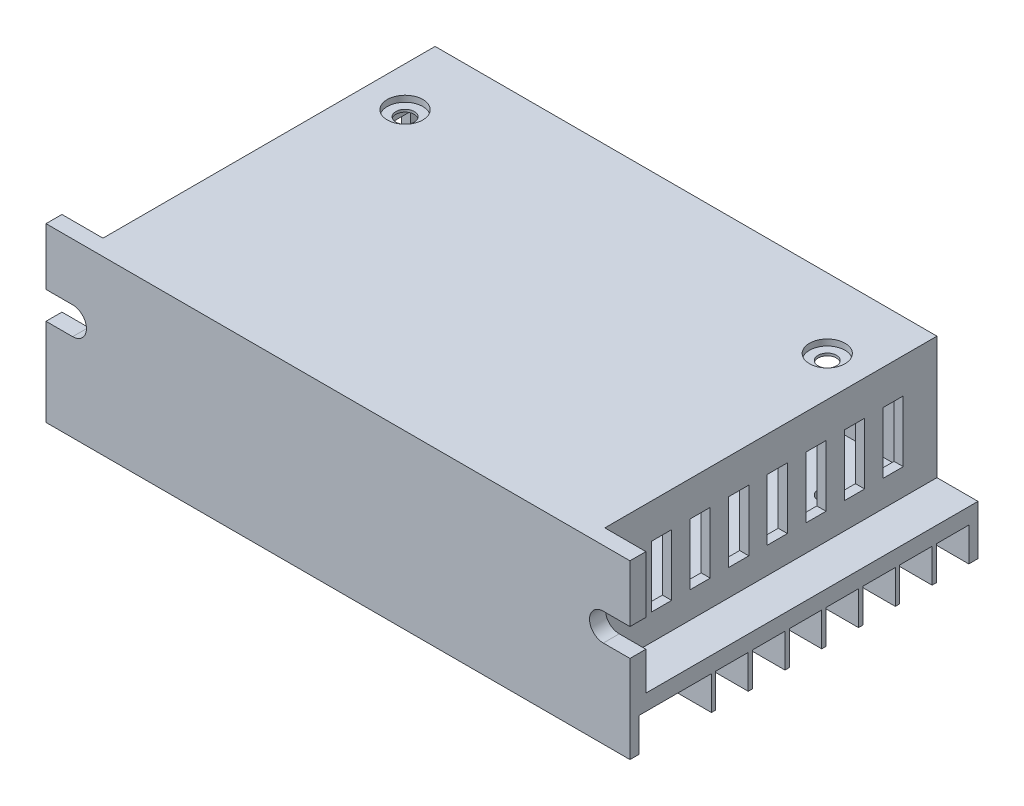
SolidWorks part; units mm, degrees
ref_plane "Front Plane" through (0, 0, 0) normal (0, 0, 1) x (1, 0, 0)
ref_plane "Top Plane" through (0, 0, 0) normal (0, 1, 0) x (1, 0, 0)
ref_plane "Right Plane" through (0, 0, 0) normal (1, 0, 0) x (0, 0, -1)
sketch "Sketch1" plane through (0, 0, 0) normal (0, 1, 0) x (1, 0, 0)
  line L1 (-47.65, 28.4) -> (47.65, 28.4)
  line L2 (-47.65, 28.4) -> (-47.65, -28.4)
  line L3 (-47.65, -28.4) -> (47.65, -28.4)
  line L4 (47.65, 28.4) -> (47.65, -28.4)
  line L5 (-47.65, 28.4) -> (47.65, -28.4) construction
  line L6 (-47.65, -28.4) -> (47.65, 28.4) construction
  point P0 (0, 0)
  dimension "D1" = 95.3
  dimension "D2" = 56.8
extrude "Boss-Extrude1" add sketch "Sketch1" along normal blind 28.1
sketch "Sketch2" plane through (-47.65, 0, 0) normal (-1, 0, 0) x (0, 0, 1)
  line L0 (-26.9, 0) -> (-26.9, 5.5)
  line L1 (-28.4, 0) -> (28.4, 0) construction
  line L2 (-26.9, 5.5) -> (-28.4, 5.5)
  line L3 (-28.4, 28.1) -> (-28.4, 0) construction
  line L4 (-28.4, 5.5) -> (-28.4, 0)
  line L5 (-28.4, 0) -> (-26.9, 0)
  line L6 (-15.6, 5.5) -> (-14.9, 5.5)
  line L7 (-21.6, 5.5) -> (-20.9, 5.5)
  line L8 (-21.6, 5.5) -> (-21.6, 0)
  line L9 (-21.6, 0) -> (-20.9, 0)
  line L10 (-20.9, 5.5) -> (-20.9, 0)
  line L11 (-15.6, 5.5) -> (-15.6, 0)
  line L12 (-14.9, 5.5) -> (-14.9, 0)
  line L13 (-15.6, 0) -> (-14.9, 0)
  line L14 (-9.6, 5.5) -> (-8.9, 5.5)
  line L15 (-9.6, 5.5) -> (-9.6, 0)
  line L16 (-8.9, 5.5) -> (-8.9, 0)
  line L17 (-9.6, 0) -> (-8.9, 0)
  line L18 (-3.6, 5.5) -> (-2.9, 5.5)
  line L19 (-3.6, 5.5) -> (-3.6, 0)
  line L20 (-2.9, 5.5) -> (-2.9, 0)
  line L21 (-3.6, 0) -> (-2.9, 0)
  line L22 (2.4, 5.5) -> (3.1, 5.5)
  line L23 (2.4, 5.5) -> (2.4, 0)
  line L24 (3.1, 5.5) -> (3.1, 0)
  line L25 (2.4, 0) -> (3.1, 0)
  line L26 (8.4, 5.5) -> (9.1, 5.5)
  line L27 (8.4, 5.5) -> (8.4, 0)
  line L28 (9.1, 5.5) -> (9.1, 0)
  line L29 (8.4, 0) -> (9.1, 0)
  line L30 (14.4, 5.5) -> (15.1, 5.5)
  line L31 (14.4, 5.5) -> (14.4, 0)
  line L32 (15.1, 5.5) -> (15.1, 0)
  line L33 (14.4, 0) -> (15.1, 0)
  line L35 (28.4, 0) -> (26.9, 0)
  line L36 (28.4, 0) -> (28.4, 5.5)
  line L37 (28.4, 5.5) -> (26.9, 5.5)
  line L38 (26.9, 0) -> (26.9, 5.5)
  line L39 (-28.4, 5.5) -> (28.4, 5.5)
  line L40 (-28.4, 5.5) -> (-28.4, 0)
  line L41 (-28.4, 0) -> (28.4, 0)
  line L42 (28.4, 5.5) -> (28.4, 0)
  line M25 (-28.4, 0) -> (28.4, 0)
  dimension "D1" = 1.5
  dimension "D2" = 5.5
  dimension "D3" = 0.7
  dimension "D4" = 5.3
  dimension "D5" = 7
extrude "Cut-Extrude2" cut sketch "Sketch2" against normal through all contours L39 L0 L8 M25 | L39 L10 L11 M25 | L39 L12 L15 M25 | L39 L16 L19 M25 | L39 L20 L23 M25 | L39 L24 L27 M25 | L39 L28 L31 M25 | L39 L32 L38 M25 region at (-47.65, 2.75, -24.25) region at (-47.65, 2.75, -18.25) region at (-47.65, 2.75, -12.25) region at (-47.65, 2.75, -6.25) region at (-47.65, 2.75, -0.25) region at (-47.65, 2.75, 5.75) region at (-47.65, 2.75, 11.75) region at (-47.65, 2.75, 21)
sketch "Sketch3" plane through (0, 0, -28.4) normal (0, 0, -1) x (-1, 0, 0)
  line L0 (-47.65, 28.1) -> (47.65, 28.1) construction
  line L1 (-40.95, 28.1) -> (40.95, 28.1)
  line L2 (-40.95, 28.1) -> (-40.95, 8.1)
  line L3 (-40.95, 8.1) -> (40.95, 8.1)
  line L4 (40.95, 28.1) -> (40.95, 8.1)
  line L5 (-47.65, 0) -> (47.65, 0) construction
  line L6 (47.65, 28.1) -> (47.65, 0) construction
  line L7 (-47.65, 28.1) -> (47.65, 28.1)
  line L8 (-47.65, 28.1) -> (-47.65, 8.1)
  line L9 (-47.65, 8.1) -> (47.65, 8.1)
  line L10 (47.65, 28.1) -> (47.65, 8.1)
  point P9 (0, 8.1)
  line M10 (47.65, 0) -> (47.65, 28.1)
  line M11 (47.65, 28.1) -> (-47.65, 28.1)
  line M12 (-47.65, 28.1) -> (-47.65, 0)
  dimension "D1" = 81.9
  dimension "D2" = 8.1
extrude "Cut-Extrude4" cut sketch "Sketch3" against normal offset from surface (54.2 mm away) 2.6 contours L9 L2 M12 M11 | L4 L9 M10 M11 region at (44.3, 18.1, -28.4) region at (-44.3, 18.1, -28.4) up to face at (0, 14.05, 28.4)
sketch "Sketch4" plane through (0, 0, 28.4) normal (0, 0, 1) x (1, 0, 0)
  line L0 (43.3, 16.55) -> (52, 16.55) construction
  line L1 (43.3, 18.8) -> (52, 18.8)
  line L2 (43.3, 14.3) -> (52, 14.3)
  line L3 (47.65, 28.1) -> (47.65, 0) construction
  line L4 (-47.65, 28.1) -> (47.65, 28.1) construction
  arc A0 (43.3, 18.8) -> (43.3, 14.3) centre (43.3, 16.55) ccw
  arc A1 (52, 14.3) -> (52, 18.8) centre (52, 16.55) ccw
  point P2 (47.65, 16.55)
  dimension "D2" = 4.35
  dimension "D1" = 4.5
  dimension "D3" = 9.3
extrude "Cut-Extrude5" cut sketch "Sketch4" against normal through all
mirror "Mirror1" about plane through (0, 0, 0) normal (1, 0, 0) of "Cut-Extrude5"
sketch "Sketch5" plane through (40.95, 0, 0) normal (1, 0, 0) x (0, 0, -1)
  line L0 (-25.8, 28.1) -> (28.4, 28.1) construction
  line L1 (-18.2, 22.4) -> (-14.9, 22.4)
  line L2 (-18.2, 22.4) -> (-18.2, 12.4)
  line L3 (-18.2, 12.4) -> (-14.9, 12.4)
  line L4 (-14.9, 22.4) -> (-14.9, 12.4)
  line L5 (-28.4, 14.3) -> (-28.4, 0) construction
  line L6 (-11.9, 22.4) -> (-8.6, 22.4)
  line L7 (-11.9, 22.4) -> (-11.9, 12.4)
  line L8 (-11.9, 12.4) -> (-8.6, 12.4)
  line L9 (-8.6, 22.4) -> (-8.6, 12.4)
  line L10 (-5.6, 22.4) -> (-2.3, 22.4)
  line L11 (-5.6, 22.4) -> (-5.6, 12.4)
  line L12 (-5.6, 12.4) -> (-2.3, 12.4)
  line L13 (-2.3, 22.4) -> (-2.3, 12.4)
  line L14 (0.7, 22.4) -> (4, 22.4)
  line L15 (0.7, 22.4) -> (0.7, 12.4)
  line L16 (0.7, 12.4) -> (4, 12.4)
  line L17 (4, 22.4) -> (4, 12.4)
  line L18 (7, 22.4) -> (10.3, 22.4)
  line L19 (7, 22.4) -> (7, 12.4)
  line L20 (7, 12.4) -> (10.3, 12.4)
  line L21 (10.3, 22.4) -> (10.3, 12.4)
  line L22 (13.3, 22.4) -> (16.6, 22.4)
  line L23 (13.3, 22.4) -> (13.3, 12.4)
  line L24 (13.3, 12.4) -> (16.6, 12.4)
  line L25 (16.6, 22.4) -> (16.6, 12.4)
  line L26 (19.6, 22.4) -> (22.9, 22.4)
  line L27 (19.6, 22.4) -> (19.6, 12.4)
  line L28 (19.6, 12.4) -> (22.9, 12.4)
  line L29 (22.9, 22.4) -> (22.9, 12.4)
  dimension "D1" = 10
  dimension "D2" = 5.7
  dimension "D3" = 3.3
  dimension "D4" = 10.2
  dimension "D5" = 7
extrude "Cut-Extrude6" cut sketch "Sketch5" against normal through all
sketch "Sketch6" plane through (0, 28.1, 0) normal (0, 1, 0) x (1, 0, 0)
  line L8 (-39.45, -25.8) -> (39.45, -25.8)
  line L9 (-40.95, -25.8) -> (-47.65, -25.8) construction
  line L16 (39.45, -26.9) -> (39.45, 26.9)
  line L17 (39.45, 26.9) -> (-39.45, 26.9)
  line L18 (-39.45, 26.9) -> (-39.45, -26.9)
  line L19 (-39.45, -26.9) -> (39.45, -26.9)
  line L20 (39.45, -25.8) -> (39.45, 26.9)
  line L21 (39.45, 26.9) -> (-39.45, 26.9)
  line L22 (-39.45, 26.9) -> (-39.45, -25.8)
  dimension "D1" = 1.5
extrude "Cut-Extrude8" cut sketch "Sketch6" against normal up to surface (20 mm away) from offset 1.4 up to face at (-44.3, 8.1, -1.3) offset against normal yes
sketch "Sketch7" plane through (-40.95, 0, 0) normal (-1, 0, 0) x (0, 0, 1)
  line L0 (-28.4, 28.1) -> (-28.4, 8.1) construction
  line L1 (-12.5, 25) -> (6.5, 25)
  line L2 (-12.5, 25) -> (-12.5, 14.5)
  line L3 (-12.5, 14.5) -> (6.5, 14.5)
  line L4 (6.5, 25) -> (6.5, 14.5)
  line L5 (25.8, 28.1) -> (-28.4, 28.1) construction
  line L6 (25.8, 8.1) -> (-28.4, 8.1) construction
  line L7 (25.8, 8.1) -> (25.8, 28.1) construction
  dimension "D1" = 15.9
  dimension "D2" = 3.1
  dimension "D3" = 6.4
  dimension "D4" = 19.3
extrude "Cut-Extrude9" cut sketch "Sketch7" against normal up to next
sketch "Sketch8" plane through (0, 0, -28.4) normal (0, 0, -1) x (-1, 0, 0)
  line L0 (-40.95, 28.1) -> (40.95, 28.1) construction
  line L1 (-33.15, 24.3) -> (33.15, 24.3)
  line L2 (-33.15, 24.3) -> (-33.15, 13.5)
  line L3 (-33.15, 13.5) -> (33.15, 13.5)
  line L4 (33.15, 24.3) -> (33.15, 13.5)
  point P4 (0, 24.3)
  dimension "D1" = 66.3
  dimension "D2" = 10.8
  dimension "D3" = 3.8
extrude "Cut-Extrude10" cut sketch "Sketch8" against normal up to next
sketch "Sketch9" plane through (0, 28.1, 0) normal (0, 1, 0) x (1, 0, 0)
  line L0 (-40.95, -25.8) -> (-40.95, 28.4) construction
  line L1 (40.95, 28.4) -> (-40.95, 28.4) construction
  point P0 (-34.45, 17)
  dimension "D1" = 6.5
  dimension "D2" = 11.4
hole_wizard "CBORE for M5 Hex Head Bolt1" positions "Sketch9" profile "Sketch10" counterbore size "M5" standard "ANSI Metric" end condition through all
sketch "Sketch10" plane through (-34.45, 28.1, -17) normal (1, 0, 0) x (0, 0, 1)
  line L0 (0, 0) -> (0, 28.1)
  line L1 (0, 28.1) -> (1.5, 28.1)
  line L3 (1.5, 28.1) -> (1.5, 1)
  line L4 (1.5, 1) -> (2.9, 1)
  line L5 (2.9, 1) -> (2.9, 0)
  line L7 (2.9, 0) -> (0, 0)
  line L11 (0, -6.35) -> (0, 107.95) construction
  dimension "Thru Hole Dia." = 3
  dimension "Thru Hole Depth" = 28.1
  dimension "C'Bore Dia." = 5.8
  dimension "C'Bore Depth" = 1
mirror "Mirror2" about plane through (0, 0, 0) normal (1, 0, 0) of "CBORE for M5 Hex Head Bolt1"
equation "\"mDriverWidth\" = 56.8"
equation "\"mDriverLength\" =95.3"
equation "\"mDriverHeight\" = 28.1"
equation "\"D1@Boss-Extrude1\"=\"mDriverHeight\""
equation "\"D2@Sketch1\"=\"mDriverWidth\""
equation "\"D1@Sketch1\"=\"mDriverLength\""
